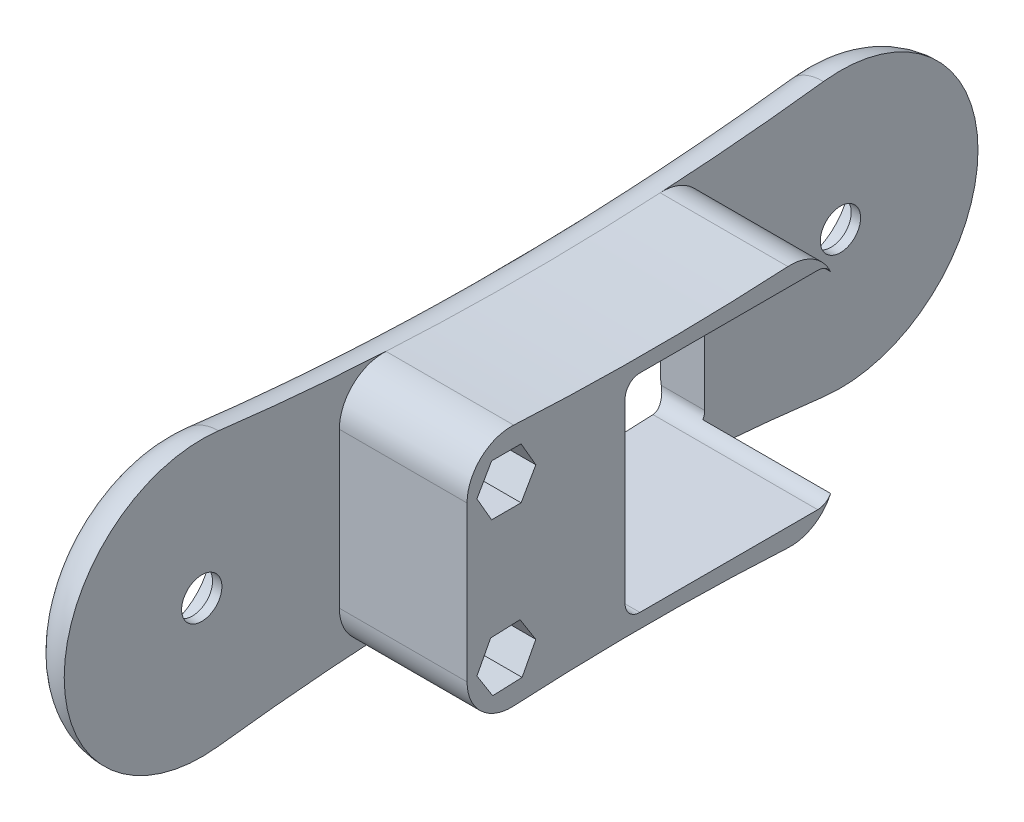
SolidWorks part; units mm, degrees
ref_plane "Front Plane" through (0, 0, 0) normal (0, 0, 1) x (1, 0, 0)
ref_plane "Top Plane" through (0, 0, 0) normal (0, 1, 0) x (1, 0, 0)
ref_plane "Right Plane" through (0, 0, 0) normal (1, 0, 0) x (0, 0, -1)
sketch "Sketch1" plane through (0, 0, 0) normal (1, 0, 0) x (0, 0, -1)
  line L0 (-188.563, 0) -> (207.6309, 0) construction
  circle A0 centre (-130, 0) radius 28
  circle A1 centre (0, 0) radius 28
  arc A2 (-126.5668, 27.7887) -> (-3.4332, 27.7887) centre (-65, 526.125) ccw
  arc A3 (-126.5668, -27.7887) -> (-3.4332, -27.7887) centre (-65, -526.125) cw
  point P13 (-65, 24)
  point P14 (-65, -24)
  dimension "D1" = 56
  dimension "D2" = 56
  dimension "D3" = 130
  dimension "D4" = 48
extrude "Boss-Extrude1" add sketch "Sketch1" along normal blind 35 contours A1 L0 | L0 A1 | A0 L0 A1 A2 | L0 A0 A3 A1 | L0 A0 | A0 L0 region at (0, 11.8836, 130) region at (0, -11.8836, 130) region at (0, 13.2362, 65) region at (0, -13.2362, 65) region at (0, 11.8836, 0) region at (0, -11.8836, 0)
sketch "Sketch4" plane through (0, 0, 0) normal (0, 1, 0) x (1, 0, 0)
  line L0 (-64.695, -65) -> (222.9919, -65) construction
  line L1 (9, 28) -> (61, 28)
  line L2 (9, 28) -> (9, -28)
  line L3 (9, -28) -> (61, -28)
  line L4 (61, 28) -> (61, -28)
  line L5 (9, 28) -> (61, -28) construction
  line L6 (9, -28) -> (61, 28) construction
  line L7 (9, -102) -> (61, -158) construction
  line L8 (9, -158) -> (61, -102) construction
  line L9 (61, -158) -> (61, -102)
  line L10 (9, -102) -> (61, -102)
  line L11 (9, -158) -> (9, -102)
  line L12 (9, -158) -> (61, -158)
  point P0 (35, 0)
  point P12 (35, -130)
  dimension "D1" = 56
  dimension "D2" = 52
  dimension "D3" = 35
  dimension "D4" = 65
extrude "Cut-Extrude1" cut sketch "Sketch4" against normal through all both and the other way through all
sketch "Sketch5" plane through (0, 0, 0) normal (1, 0, 0) x (0, 0, -1)
  line L1 (-33.225, -15.5) -> (-64.225, -15.5) construction
  line L2 (-33.225, -15.5) -> (-33.225, 15.5) construction
  line L3 (-33.225, 15.5) -> (-64.225, 15.5) construction
  line L4 (-64.225, -15.5) -> (-64.225, 15.5) construction
  line L5 (-33.225, -15.5) -> (-64.225, 15.5) construction
  line L6 (-33.225, 15.5) -> (-64.225, -15.5) construction
  circle A8 centre (-33.225, -15.5) radius 1.6
  circle A9 centre (-33.225, 15.5) radius 1.6
  circle A10 centre (-64.225, -15.5) radius 1.6
  circle A11 centre (-64.225, 15.5) radius 1.6
  circle A12 centre (-33.225, -15.5) radius 3
  circle A13 centre (-33.225, 15.5) radius 3
  circle A14 centre (-64.225, -15.5) radius 3
  circle A15 centre (-64.225, 15.5) radius 3
  point P0 (-48.725, 0)
  dimension "D4" = 3.2
  dimension "D5" = 6
  dimension "D1" = 48.725
  dimension "D2" = 31
  dimension "D3" = 31
sketch "Sketch6" plane through (0, 0, 0) normal (1, 0, 0) x (0, 0, -1)
  line L1 (-30.625, -21.1) -> (-66.825, -21.1)
  line L2 (-27.625, -18.1) -> (-27.625, 18.1)
  line L3 (-30.625, 21.1) -> (-66.825, 21.1)
  line L4 (-69.825, -18.1) -> (-69.825, 18.1)
  line L5 (-27.625, -21.1) -> (-69.825, 21.1) construction
  line L6 (-27.625, 21.1) -> (-69.825, -21.1) construction
  arc A0 (-66.825, 21.1) -> (-69.825, 18.1) centre (-66.825, 18.1) ccw
  arc A1 (-66.825, -21.1) -> (-69.825, -18.1) centre (-66.825, -18.1) cw
  arc A2 (-27.625, 18.1) -> (-30.625, 21.1) centre (-30.625, 18.1) ccw
  arc A3 (-30.625, -21.1) -> (-27.625, -18.1) centre (-30.625, -18.1) ccw
  point P0 (-48.725, 0)
  dimension "D1" = 48.725
  dimension "D4" = 3
  dimension "D2" = 42.2
  dimension "D3" = 42.2
sketch "Sketch7" plane through (0, 0, 0) normal (1, 0, 0) x (0, 0, -1)
  circle A0 centre (0, 0) radius 4.1
  circle A1 centre (-130, 0) radius 4.1
  circle A2 centre (0, 0) radius 11.1
  circle A3 centre (-130, 0) radius 11.1
  dimension "D3" = 130
  dimension "D1" = 8.2
  dimension "D2" = 22.2
ref_plane "Plane1" through (35, 0, 0) normal (1, 0, 0) x (0, 0, -1)
extrude "Cut-Extrude2" cut sketch "Sketch6" along normal through all
sketch "Sketch8" plane through (0, 0, 0) normal (1, 0, 0) x (0, 0, -1)
  line L0 (0, 0) -> (-165.6952, 0) construction
  line L1 (-100, 15.5) -> (-97, 10.3038)
  line L2 (-97, 10.3038) -> (-91, 10.3038)
  line L3 (-91, 10.3038) -> (-88, 15.5)
  line L4 (-88, 15.5) -> (-91, 20.6962)
  line L5 (-91, 20.6962) -> (-97, 20.6962)
  line L6 (-97, 20.6962) -> (-100, 15.5)
  line L7 (-99.9952, -15.7395) -> (-96.7902, -20.8118)
  line L8 (-96.7902, -20.8118) -> (-90.7949, -20.5722)
  line L9 (-90.7949, -20.5722) -> (-88.0048, -15.2605)
  line L10 (-88.0048, -15.2605) -> (-91.2098, -10.1882)
  line L11 (-91.2098, -10.1882) -> (-97.2051, -10.4278)
  line L12 (-97.2051, -10.4278) -> (-99.9952, -15.7395)
  circle A0 centre (-94, 15.5) radius 5.1962 construction
  circle A1 centre (-94, -15.5) radius 5.1962 construction
  dimension "D3" = 31
  dimension "D1" = 6
  dimension "D2" = 94
extrude "Cut-Extrude3" cut sketch "Sketch8" along normal through all
extrude "Cut-Extrude4" cut sketch "Sketch7" along normal up to next contours A1 | A0
extrude "Cut-Extrude5" cut sketch "Sketch7<3>" along normal blind 7.1 contours A3 | A2
sketch "Sketch7<3>" plane through (0, 0, 0) normal (1, 0, 0) x (0, 0, -1) same geometry as "Sketch7"
fillet "Fillet1" radius 9 4 edges at (0, 0, 158) (0, 24, 65) (0, 0, -28) (0, -24, 65)
fillet "Fillet2" radius 9 4 edges at (22, -25.3651, 28) (22, -25.3651, 102) (22, 25.3651, 28) (22, 25.3651, 102)
equation "\"top dia\"= 56"
equation "\"D1@Sketch1\"=\"top dia\""
equation "\"bottom dia\"= 56"
equation "\"D2@Sketch1\"=\"bottom dia\""
equation "\"arm length\"= 130"
equation "\"D3@Sketch1\"=\"arm length\""
equation "\"across\"= 48"
equation "\"D4@Sketch1\"=\"across\""
equation "\"arm width\"=70"
equation "\"D1@Boss-Extrude1\"=\"arm width\"/2"
equation "\"D1@Sketch4\"=\"bottom dia\""
equation "\"D2@Sketch4\"=\"arm width\" - (7+2)*2"
equation "\"D3@Sketch4\"=\"arm width\"/2"
equation "\"D4@Sketch4\"=\"arm length\"/2"
equation "\"gear dist\"= 48.725"
equation "\"D1@Sketch5\"=\"gear dist\""
equation "\"D1@Sketch6\"=\"gear dist\""
equation "\"D3@Sketch7\"=\"arm length\" "
equation "\"D1@Plane1\"= \"arm width\" / 2"
equation "\"D2@Sketch8\"=\"arm length\"-\"top dia\"/2 - 8"
equation "\"stepper hole dist\"= 31"
equation "\"D2@Sketch5\"= \"stepper hole dist\""
equation "\"D3@Sketch5\"= \"stepper hole dist\""
equation "\"D3@Sketch8\"= \"stepper hole dist\""
equation "\"bearing depth\"=7.1"
equation "\"D1@Cut-Extrude5\"=\"bearing depth\""
equation "\"hex nut size\"=6"
equation "\"D1@Sketch8\"=\"hex nut size\""
equation "\"stepper motor width\"=42.2"
equation "\"D3@Sketch6\"=\"stepper motor width\""
equation "\"D2@Sketch6\"=\"stepper motor width\""
equation "\"M3 hole size\"= 3.2"
equation "\"D4@Sketch5\"= \"M3 hole size\""
equation "\"bearing bore\"=8.2"
equation "\"D1@Sketch7\"=\"bearing bore\""
equation "\"bearing OD\"=22.2"
equation "\"D2@Sketch7\"=\"bearing OD\""
equation "\"M3 bolt head\"=6"
equation "\"D5@Sketch5\"=\"M3 bolt head\""
